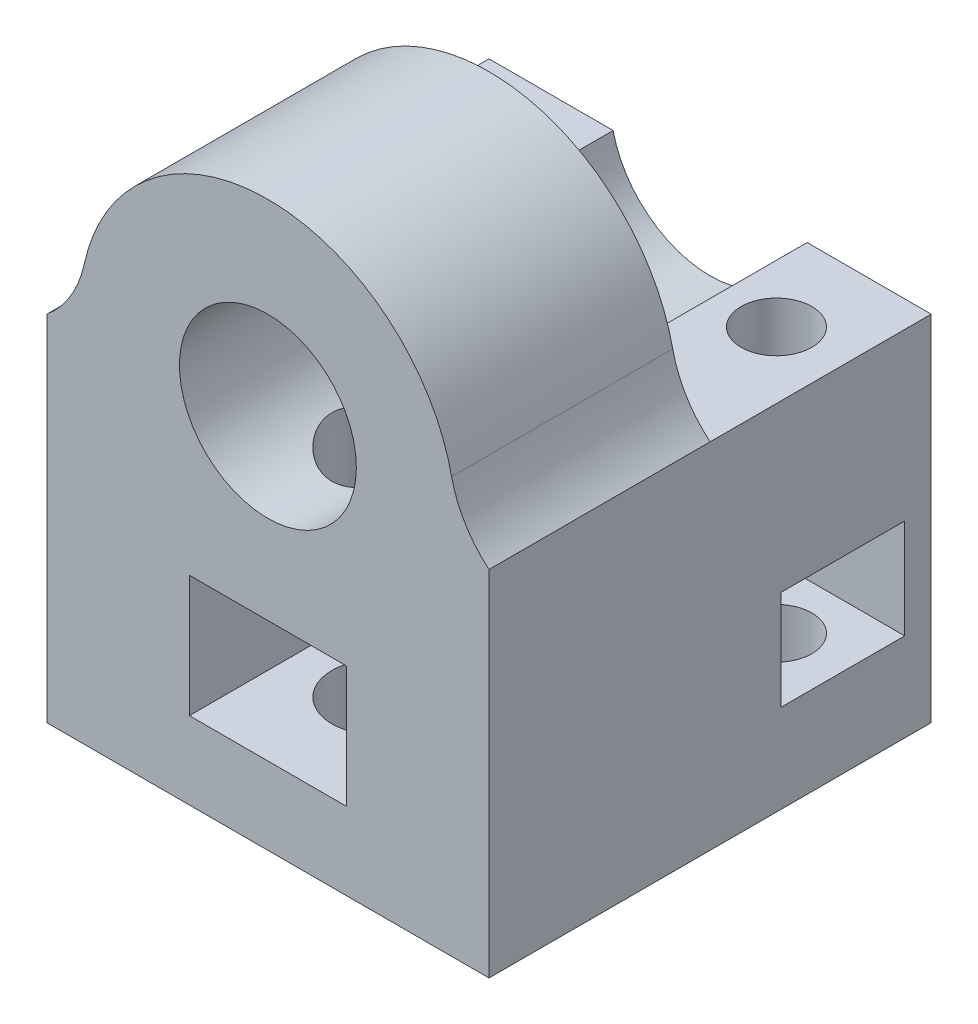
SolidWorks part; units mm, degrees
material "3D printed plastic"
ref_plane "Front Plane" through (0, 0, 0) normal (0, 0, 1) x (1, 0, 0)
ref_plane "Top Plane" through (0, 0, 0) normal (0, 1, 0) x (1, 0, 0)
ref_plane "Right Plane" through (0, 0, 0) normal (1, 0, 0) x (0, 0, -1)
sketch "Sketch1" plane through (0, 0, 0) normal (0, 0, 1) x (1, 0, 0)
  line L0 (0, 0) -> (0, -17) construction
  line L2 (-8, -2.8723) -> (-8, -17)
  line L3 (-8, -17) -> (8, -17)
  line L4 (8, -2.8723) -> (8, -17)
  circle A0 centre (0, 0) radius 4
  arc A1 (8, -2.8723) -> (-8, -2.8723) centre (0, 0) ccw
  dimension "D1" = 16
  dimension "D2" = 8
  dimension "D4" = 8.5
  dimension "D3" = 17
extrude "Boss-Extrude1" add sketch "Sketch1" along normal mid plane 10
sketch "Sketch4" plane through (0, 0, -5) normal (0, 0, -1) x (-1, 0, 0)
  line L0 (-10, -1) -> (-4.3875, -1)
  line L1 (0, 0) -> (0, -1) construction
  line L2 (4.3875, -1) -> (10, -1)
  line L3 (-4.3875, -1) -> (4.3875, -1) construction
  line L4 (-10, -1) -> (-10, -17)
  line L5 (-10, -17) -> (10, -17)
  line L6 (10, -17) -> (10, -1)
  line L7 (8, -17) -> (-8, -17) construction
  arc A0 (-4.3875, -1) -> (4.3875, -1) centre (0, 0) ccw
  circle A1 centre (0, 0) radius 4 construction
  dimension "D2" = 0.5
  dimension "D1" = 1
  dimension "D3" = 20
extrude "Boss-Extrude2" add sketch "Sketch4" along normal blind 10 and the other way up to surface (10 mm away) other way up to face at (0, -7.0931, 5)
sketch "Sketch2" plane through (0, -17, 0) normal (0, -1, 0) x (1, 0, 0)
  circle A0 centre (0, 0) radius 2.1
  dimension "D1" = 4.2
extrude "Cut-Extrude1" cut sketch "Sketch2" against normal up to next
sketch "Sketch3" plane through (0, -17, 0) normal (0, -1, 0) x (1, 0, 0)
  line L0 (-3.55, 2.0496) -> (-3.55, 5)
  line L1 (0, 4.0992) -> (-3.55, 2.0496) construction
  line L2 (-3.55, 2.0496) -> (-3.55, -2.0496)
  line L3 (-3.55, -2.0496) -> (0, -4.0992)
  line L4 (0, -4.0992) -> (3.55, -2.0496)
  line L5 (3.55, -2.0496) -> (3.55, 2.0496)
  line L6 (3.55, 2.0496) -> (0, 4.0992) construction
  line L7 (-10, 5) -> (10, 5) construction
  line L8 (-3.55, 5) -> (3.55, 5)
  line L9 (3.55, 5) -> (3.55, 2.0496)
  circle A0 centre (0, 0) radius 3.55 construction
  dimension "D1" = 7.1
extrude "Cut-Extrude2" cut sketch "Sketch3" against normal blind 5.5 from offset 3.5 offset against normal yes
fillet "Fillet1" radius 5 2 edges at (-8.441, -1, 0) (8.441, -1, 0)
sketch "Sketch5" plane through (0, -17, 0) normal (0, -1, 0) x (1, 0, 0)
  line L0 (-7, -11) -> (7, -11) construction
  line L1 (0, -11) -> (0, 0) construction
  line L2 (10, -15) -> (-10, -15) construction
  line L3 (-10, 5) -> (-10, -15) construction
  circle A0 centre (7, -11) radius 1.6
  circle A1 centre (-7, -11) radius 1.6
  dimension "D1" = 4
  dimension "D2" = 3.2
  dimension "D3" = 3
extrude "Cut-Extrude3" cut sketch "Sketch5" against normal through all
sketch "Sketch6" plane through (0, -17, 0) normal (0, -1, 0) x (1, 0, 0)
  line L0 (-8.6166, -8.2) -> (-10, -8.2)
  line L1 (-10.2332, -11) -> (-8.6166, -13.8) construction
  line L2 (-8.6166, -13.8) -> (-5.3834, -13.8)
  line L3 (-5.3834, -13.8) -> (-3.7668, -11)
  line L4 (-3.7668, -11) -> (-5.3834, -8.2)
  line L5 (-5.3834, -8.2) -> (-8.6166, -8.2)
  line L6 (-8.6166, -8.2) -> (-10.2332, -11) construction
  line L7 (10.2332, -11) -> (8.6166, -8.2) construction
  line L8 (8.6166, -8.2) -> (5.3834, -8.2)
  line L9 (5.3834, -8.2) -> (3.7668, -11)
  line L10 (3.7668, -11) -> (5.3834, -13.8)
  line L11 (5.3834, -13.8) -> (8.6166, -13.8)
  line L12 (8.6166, -13.8) -> (10.2332, -11) construction
  line L13 (-10, 5) -> (-10, -15) construction
  line L14 (-10, -8.2) -> (-10, -13.8)
  line L15 (-10, -13.8) -> (-8.6166, -13.8)
  line L16 (8.6166, -13.8) -> (10, -13.8)
  line L17 (10, 5) -> (10, -15) construction
  line L18 (10, -13.8) -> (10, -8.2)
  line L19 (10, -8.2) -> (8.6166, -8.2)
  circle A0 centre (-7, -11) radius 2.8 construction
  circle A1 centre (7, -11) radius 2.8 construction
  dimension "D1" = 5.6
extrude "Cut-Extrude4" cut sketch "Sketch6" against normal blind 4.5 from offset 4 offset against normal yes
